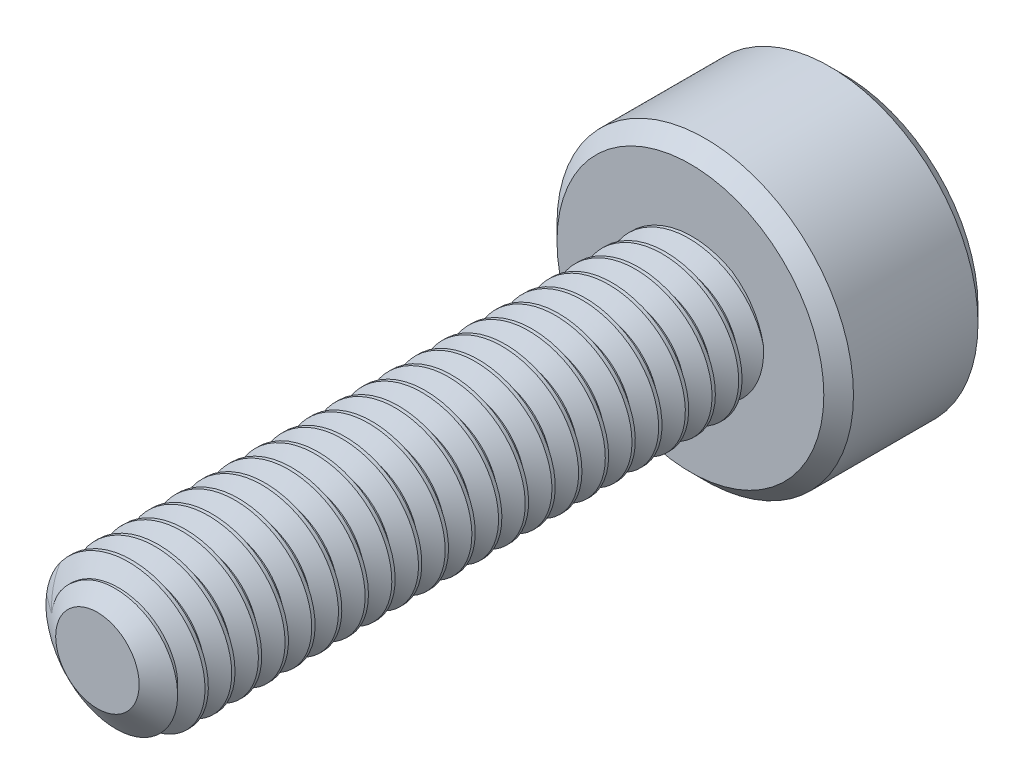
SolidWorks part; units mm, degrees
ref_plane "Front Plane" through (0, 0, 0) normal (0, 0, 1) x (1, 0, 0)
ref_plane "Top Plane" through (0, 0, 0) normal (0, 1, 0) x (1, 0, 0)
ref_plane "Right Plane" through (0, 0, 0) normal (1, 0, 0) x (0, 0, -1)
sketch "Sketch1" plane through (0, 0, 0) normal (0, 0, 1) x (1, 0, 0)
  circle A0 centre (0, 0) radius 1.25
  dimension "OD" = 2.5
extrude "Extrude1" add sketch "Sketch1" against normal blind 10
sketch "Sketch2" plane through (0, 0, 0) normal (0, 0, 1) x (1, 0, 0)
  circle A0 centre (0, 0) radius 1.25 construction
  circle A1 centre (0, 0) radius 1.25
curve "Helix/Spiral1" pitch 0.45 height 10.45 radius 1.25 centre (0, 0, 0) axis (0, 0, -1) start towards (0, 1, 0) parameters "pitch"=0.45
sketch "Sketch3" plane through (0, 0, 0) normal (1, 0, 0) x (0, 0, -1)
  line L0 (-0.3937, 1.25) -> (-0.225, 0.9577)
  line L1 (-0.225, 0.9577) -> (-0.1687, 0.9577)
  line L2 (-0.1687, 0.9577) -> (0, 1.25)
  line L3 (-0.3937, 1.25) -> (0, 1.25)
  line L4 (-0.1969, 1.25) -> (-0.1969, 0.9577) construction
  line L5 (-0.3094, 1.1039) -> (-0.0844, 1.1039) construction
  line L6 (0, 1.25) -> (0, -1.25) construction
  dimension "D1" = 0.0563
  dimension "D2" = 0.225
  dimension "D3" = 60
sweep "Cut-Sweep1" cut profiles "Sketch3" path "Helix/Spiral1"
sketch "Sketch4" plane through (0, 0, 0) normal (1, 0, 0) x (0, 0, -1)
  line L0 (0.3825, 1.25) -> (0, 0.7037)
  line L1 (0, 0.7037) -> (0, 1.25)
  line L2 (0.3825, 1.25) -> (0, 1.25)
  line L3 (-0.3937, 1.25) -> (0, 1.25) construction
  line L4 (0, 0) -> (7.0209, 0) construction
  dimension "D1" = 55
  dimension "D2" = 0.254
revolve "Cut-Revolve1" cut sketch "Sketch4" angle 360 about L4
sketch "Sketch5" plane through (0, 0, 0) normal (1, 0, 0) x (0, 0, -1)
  line L0 (10, -0.1596) -> (10, 1.1799) construction
  line L1 (10, 1.377) -> (87.4327, 1.377)
  line L2 (10, 1.377) -> (10, 0)
  line L3 (10, 0) -> (87.3125, 0)
  line L4 (87.3125, 1.0468) -> (87.3125, 0)
  line L5 (87.4327, 1.377) -> (87.3125, 1.0468)
  line L6 (0, 0) -> (9.9695, 0) construction
  point P3 (87.3125, 1.377)
  point P10 (87.3125, 1.377)
  dimension "D1" = 0.3302
  dimension "Thread min" = 87.3125
  dimension "D2" = 0.127
  dimension "D3" = 20
revolve "partially thread" [suppressed] add sketch "Sketch5" angle 360 about L6
sketch "Sketch6" plane through (0, 0, -10) normal (0, 0, -1) x (-1, 0, 0)
  circle A0 centre (0, 0) radius 2.5
  dimension "head dia" = 5
extrude "Extrude2" add sketch "Sketch6" along normal blind 2.6
sketch "Sketch7" plane through (0, 0, -12.6) normal (0, 0, -1) x (-1, 0, 0)
  line L1 (0, 1.1547) -> (-1, 0.5774)
  line L2 (-1, 0.5774) -> (-1, -0.5774)
  line L3 (-1, -0.5774) -> (0, -1.1547)
  line L4 (0, -1.1547) -> (1, -0.5774)
  line L5 (1, -0.5774) -> (1, 0.5774)
  line L6 (1, 0.5774) -> (0, 1.1547)
  circle A0 centre (0, 0) radius 1 construction
  dimension "hex dia" = 2
extrude "Cut-Extrude1" cut sketch "Sketch7" against normal blind 1.5
sketch "Sketch8" plane through (0, 0, -12.6) normal (0, 0, -1) x (-1, 0, 0)
  circle A0 centre (0, 0) radius 1.1547
extrude "Cut-Extrude2" cut sketch "Sketch8" against normal through all draft 45
chamfer "Chamfer1" distance 0.25 angle 45 2 edges at (-2.5, 0, -12.6) (-2.5, 0, -10)
sketch "Sketch9" plane through (0, 0, 0) normal (1, 0, 0) x (0, 0, -1)
  line L0 (0, 1.25) -> (0, -1.25) construction
  line L1 (2.475, 1.25) -> (2.475, -1.25) construction
  dimension "D1" = 2.475
  dimension "D4" = 0.635
  dimension "D5" = 0.3302
equation "\"D3@Helix/Spiral1\" = \"screw length@Extrude1\"+\"pitch@Helix/Spiral1\""
equation "\"D1@Sketch3\" = \"pitch@Helix/Spiral1\"*.125"
equation "\"D2@Sketch3\" = \"pitch@Helix/Spiral1\"*.5"
equation "\"D1@Cut-Extrude1\" = \"hex dia@Sketch7\"*.75"
equation "\"D1@Chamfer1\" = \"head dia@Sketch6\"*.05"
equation "\"D1@Sketch9\" = \"pitch@Helix/Spiral1\"*5.5"
